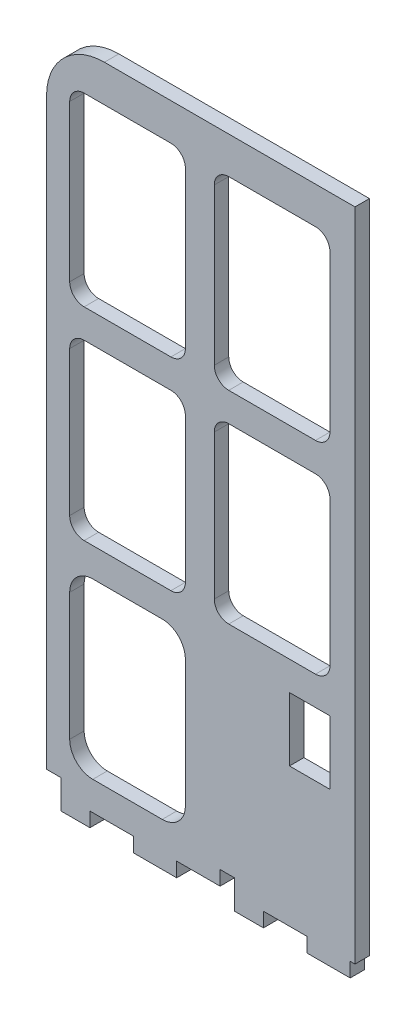
SolidWorks part; units mm, degrees
material "Balsa"
ref_plane "Front Plane" through (0, 0, 0) normal (0, 0, 1) x (1, 0, 0)
ref_plane "Top Plane" through (0, 0, 0) normal (0, 1, 0) x (1, 0, 0)
ref_plane "Right Plane" through (0, 0, 0) normal (1, 0, 0) x (0, 0, -1)
sketch "Sketch1" plane through (0, 0, 0) normal (0, 0, 1) x (1, 0, 0)
  line L1 (135.4577, 0) -> (135.4577, 287.9852)
  line L2 (135.4577, 287.9852) -> (25.4, 287.9852)
  line L4 (0, 0) -> (0, -6.35)
  line L6 (0, 0) -> (0, -6.35)
  line L7 (0, -6.35) -> (19.05, -6.35)
  line L8 (19.05, 0) -> (19.05, -6.35)
  line L10 (38.1, 0) -> (38.1, -6.35)
  line L11 (38.1, -6.35) -> (57.15, -6.35)
  line L12 (57.15, 0) -> (57.15, -6.35)
  line L14 (76.2, 0) -> (76.2, -6.35)
  line L15 (76.2, -6.35) -> (95.25, -6.35)
  line L16 (95.25, 0) -> (95.25, -6.35)
  line L18 (114.3, 0) -> (114.3, -6.35)
  line L19 (114.3, -6.35) -> (133.35, -6.35)
  line L20 (133.35, 0) -> (133.35, -6.35)
  line L25 (19.05, 0) -> (38.1, 0)
  line L26 (57.15, 0) -> (76.2, 0)
  line L27 (95.25, 0) -> (114.3, 0)
  line L28 (133.35, 0) -> (135.4577, 0)
  line L30 (0, 262.5852) -> (0, 0)
  line L31 (25.4, 287.9852) -> (135.4577, 287.9852)
  line L32 (19.05, 0) -> (38.1, 0)
  line L33 (38.1, -6.35) -> (57.15, -6.35)
  line L34 (57.15, 0) -> (76.2, 0)
  arc A0 (25.4, 287.9852) -> (0, 262.5852) centre (25.4, 262.5852) ccw
  point P8 (0, 287.9852)
  point P11 (135.4577, 287.9852)
  dimension "D4" = 6.35
  dimension "D5" = 19.05
  dimension "D1" = 135.4577
  dimension "D2" = 287.9852
  dimension "D3" = 135.4577
  dimension "D6" = 6.35
  dimension "D7" = 19.05
  dimension "D8" = 19.05
  dimension "D9" = 19.05
  dimension "D10" = 19.05
  dimension "D11" = 6.35
  dimension "D12" = 19.05
  dimension "D13" = 19.05
  dimension "D14" = 6.35
  dimension "D15" = 6.35
  dimension "D16" = 0
  dimension "D17" = 262.5852
  dimension "D21" = 6.35
  dimension "D22" = 6.35
  dimension "D23" = 6.35
extrude "Boss-Extrude1" add sketch "Sketch1" along normal blind 6.35 contours L2 A0 L30 L4 L7 L8 L25 L10 L11 L12 L26 L14 L15 L16 L27 L18 L19 L20 L1 region at (67.9342, 141.6966, 0)
sketch "Sketch2" plane through (0, 0, 6.35) normal (0, 0, 1) x (1, 0, 0)
  line L38 (73.66, 22.86) -> (73.66, 78.74)
  line L39 (20.32, 12.7) -> (50.8, 12.7)
  line L40 (73.66, 196.85) -> (73.66, 265.43)
  line L41 (80.01, 190.5) -> (118.11, 190.5)
  line L42 (124.46, 196.85) -> (124.46, 265.43)
  line L43 (80.01, 271.78) -> (118.11, 271.78)
  line L45 (10.16, 196.85) -> (10.16, 265.43)
  line L46 (16.51, 190.5) -> (54.61, 190.5)
  line L47 (60.96, 196.85) -> (60.96, 265.43)
  line L48 (16.51, 271.78) -> (54.61, 271.78)
  line L49 (73.66, 107.95) -> (73.66, 171.45)
  line L50 (80.01, 101.6) -> (118.11, 101.6)
  line L51 (124.46, 107.95) -> (124.46, 171.45)
  line L52 (80.01, 177.8) -> (118.11, 177.8)
  line L53 (10.16, 107.95) -> (10.16, 171.45)
  line L54 (16.51, 101.6) -> (54.61, 101.6)
  line L55 (60.96, 107.95) -> (60.96, 171.45)
  line L56 (16.51, 177.8) -> (54.61, 177.8)
  line L68 (10.16, 22.86) -> (10.16, 78.74)
  line L69 (20.32, 88.9) -> (50.8, 88.9)
  line L70 (60.96, 22.86) -> (60.96, 78.74)
  line L71 (83.82, 12.7) -> (114.3, 12.7)
  line L72 (124.46, 22.86) -> (124.46, 78.74)
  line L73 (83.82, 88.9) -> (114.3, 88.9)
  line L104 (19.05, -38.1) -> (44.45, -38.1) [skipped]
  line L105 (137.16, 19.05) -> (137.16, 82.55) [skipped]
  line L106 (146.05, 12.7) -> (171.45, 12.7) [skipped]
  line L107 (187.96, 19.05) -> (187.96, 82.55) [skipped]
  line L108 (146.05, 88.9) -> (171.45, 88.9) [skipped]
  line L109 (137.16, -44.45) -> (137.16, 19.05) [skipped]
  line L110 (146.05, -50.8) -> (171.45, -50.8) [skipped]
  line L111 (187.96, -44.45) -> (187.96, 19.05) [skipped]
  line L112 (146.05, 25.4) -> (171.45, 25.4) [skipped]
  line L113 (137.16, -103.373) -> (137.16, -49.027) [skipped]
  line L114 (150.627, -114.3) -> (166.873, -114.3) [skipped]
  line L115 (187.96, -103.373) -> (187.96, -49.027) [skipped]
  line L116 (150.627, -38.1) -> (166.873, -38.1) [skipped]
  line L117 (73.66, -97.4702) -> (73.66, -54.9298) [skipped]
  line L118 (124.46, -97.4702) -> (124.46, -54.9298) [skipped]
  line L119 (93.0298, -114.3) -> (97.4702, -114.3) [skipped]
  line L120 (93.0298, -38.1) -> (97.4702, -38.1) [skipped]
  line L121 (10.16, -105.3232) -> (10.16, -47.0768) [skipped]
  line L122 (37.2067, -114.3) -> (48.1202, -114.3) [skipped]
  line L123 (60.96, -105.3232) -> (60.96, -58.7589) [skipped]
  line L124 (19.05, 25.4) -> (44.45, 25.4) [skipped]
  line L125 (60.96, -50.8) -> (60.96, 25.4) [skipped]
  line L126 (19.05, -50.8) -> (44.45, -50.8) [skipped]
  line L127 (10.16, -50.8) -> (10.16, 25.4) [skipped]
  line L128 (124.46, -69.3053) -> (124.46, 6.8947) [skipped]
  line L129 (73.66, -50.8) -> (73.66, 25.4) [skipped]
  line L130 (94.7053, 25.4) -> (103.4599, 25.4) [skipped]
  line L131 (94.7053, -50.8) -> (103.4599, -50.8) [skipped]
  arc A24 (73.66, 78.74) -> (83.82, 88.9) centre (83.82, 78.74) cw
  arc A25 (124.46, 78.74) -> (114.3, 88.9) centre (114.3, 78.74) ccw
  arc A26 (114.3, 12.7) -> (124.46, 22.86) centre (114.3, 22.86) ccw
  arc A27 (73.66, 22.86) -> (83.82, 12.7) centre (83.82, 22.86) ccw
  arc A28 (50.8, 12.7) -> (60.96, 22.86) centre (50.8, 22.86) ccw
  arc A29 (50.8, 88.9) -> (60.96, 78.74) centre (50.8, 78.74) cw
  arc A30 (10.16, 78.74) -> (20.32, 88.9) centre (20.32, 78.74) cw
  arc A31 (20.32, 12.7) -> (10.16, 22.86) centre (20.32, 22.86) cw
  arc A57 (10.16, 196.85) -> (16.51, 190.5) centre (16.51, 196.85) ccw
  arc A58 (10.16, 265.43) -> (16.51, 271.78) centre (16.51, 265.43) cw
  arc A59 (60.96, 265.43) -> (54.61, 271.78) centre (54.61, 265.43) ccw
  arc A60 (54.61, 190.5) -> (60.96, 196.85) centre (54.61, 196.85) ccw
  arc A61 (73.66, 196.85) -> (80.01, 190.5) centre (80.01, 196.85) ccw
  arc A62 (73.66, 265.43) -> (80.01, 271.78) centre (80.01, 265.43) cw
  arc A63 (124.46, 265.43) -> (118.11, 271.78) centre (118.11, 265.43) ccw
  arc A64 (118.11, 190.5) -> (124.46, 196.85) centre (118.11, 196.85) ccw
  arc A65 (10.16, 107.95) -> (16.51, 101.6) centre (16.51, 107.95) ccw
  arc A66 (10.16, 171.45) -> (16.51, 177.8) centre (16.51, 171.45) cw
  arc A67 (60.96, 171.45) -> (54.61, 177.8) centre (54.61, 171.45) ccw
  arc A68 (54.61, 101.6) -> (60.96, 107.95) centre (54.61, 107.95) ccw
  arc A69 (73.66, 107.95) -> (80.01, 101.6) centre (80.01, 107.95) ccw
  arc A70 (73.66, 171.45) -> (80.01, 177.8) centre (80.01, 171.45) cw
  arc A71 (124.46, 171.45) -> (118.11, 177.8) centre (118.11, 171.45) ccw
  arc A72 (118.11, 101.6) -> (124.46, 107.95) centre (118.11, 107.95) ccw
  point P88 (60.96, 12.7)
  point P93 (10.16, 88.9)
  point P96 (10.16, 12.7)
  dimension "D7" = 81.28
  dimension "D12" = 76.2
  dimension "D11" = 50.8
  dimension "D1" = 76.2
  dimension "D2" = 50.8
  dimension "D3" = 3
  dimension "D4" = 3
  dimension "D5" = 10.16
  dimension "D6" = 12.7
  dimension "D8" = 12.7
  dimension "D9" = 81.28
  dimension "D10" = 50.8
  dimension "D13" = 76.2
  dimension "D14" = 50.8
  dimension "D15" = 50.8
  dimension "D16" = 12.7
  dimension "D17" = 12.7
  dimension "D18" = 0
  dimension "D19" = 0
  dimension "D20" = 12.7
  dimension "D21" = 12.7
  dimension "D22" = 12.7
  dimension "D23" = 12.7
extrude "Cut-Extrude1" cut sketch "Sketch2" against normal through all
sketch "Sketch3" plane through (0, 0, 6.35) normal (0, 0, 1) x (1, 0, 0)
  line L1 (0, -6.35) -> (6.35, -6.35)
  line L2 (0, -6.35) -> (0, 6.35)
  line L3 (0, 6.35) -> (6.35, 6.35)
  line L4 (6.35, -6.35) -> (6.35, 6.35)
  line L5 (76.2, -6.35) -> (82.55, -6.35)
  line L6 (76.2, -6.35) -> (76.2, 6.35)
  line L7 (76.2, 6.35) -> (82.55, 6.35)
  line L8 (82.55, -6.35) -> (82.55, 6.35)
  dimension "D1" = 6.35
  dimension "D2" = 12.7
  dimension "D3" = 6.35
  dimension "D4" = 12.7
extrude "Cut-Extrude2" cut sketch "Sketch3" against normal through all
sketch "Sketch4" plane through (0, 0, 6.35) normal (0, 0, 1) x (1, 0, 0)
  line L5 (69.1558, 89.874) -> (128.0503, 89.874)
  line L6 (69.1558, 89.874) -> (69.1558, 9.4409)
  line L7 (69.1558, 9.4409) -> (128.0503, 9.4409)
  line L8 (128.0503, 89.874) -> (128.0503, 9.4409)
  dimension "D1" = 80.433
extrude "Boss-Extrude3" add sketch "Sketch4" against normal up to surface (6.35 mm away) from surface contours L8 L7 L6 L5 up to face at (99.06, 50.8, 0) starting at face at (66.7676, 35.5833, 6.35)
ref_plane "Plane1" through (50.8, 88.9, 0) normal (-1, 0, 0) x (0, 0, 1)
sketch "Sketch6" plane through (0, 0, 0) normal (0, 0, -1) x (-1, 0, 0)
  line L1 (-124.46, 88.9) -> (-106.68, 88.9)
  line L2 (-124.46, 88.9) -> (-124.46, 60.96)
  line L3 (-124.46, 60.96) -> (-106.68, 60.96)
  line L4 (-106.68, 88.9) -> (-106.68, 60.96)
  dimension "D1" = 17.78
  dimension "D2" = 27.94
extrude "Cut-Extrude3" cut sketch "Sketch6" against normal through all
